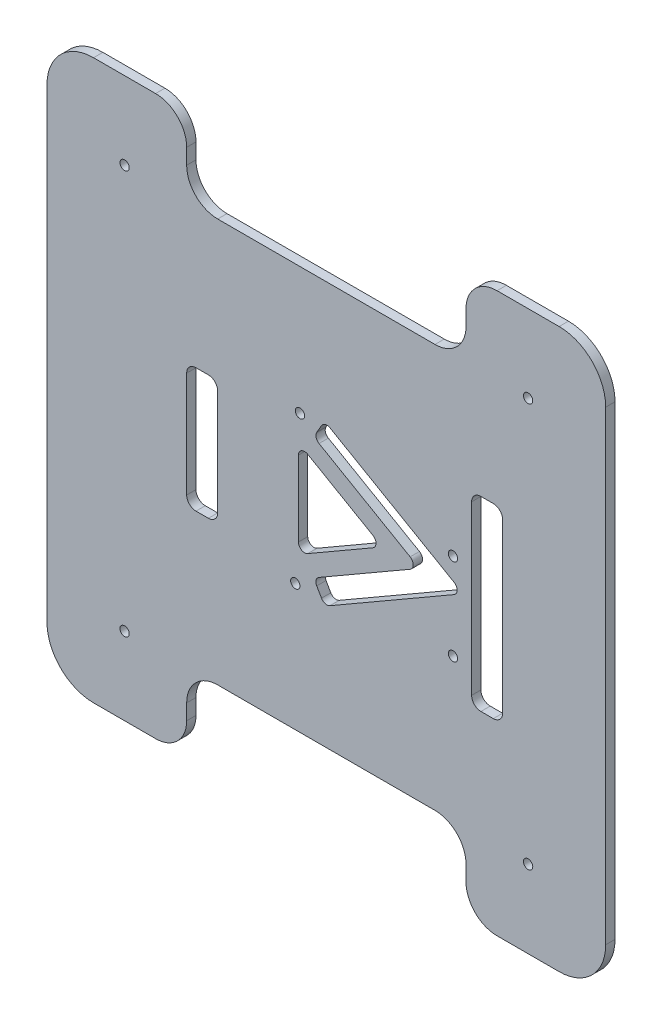
SolidWorks part; units mm, degrees
ref_plane "Front" through (0, 0, 0) normal (0, 0, 1) x (1, 0, 0)
ref_plane "Top" through (0, 0, 0) normal (0, 1, 0) x (1, 0, 0)
ref_plane "Right" through (0, 0, 0) normal (1, 0, 0) x (0, 0, -1)
sketch "Эскиз1" plane through (0, 0, 0) normal (0, 0, 1) x (1, 0, 0)
  line L1 (75, -90) -> (-75, -90)
  line L2 (90, -75) -> (90, 75)
  line L3 (75, 90) -> (-75, 90)
  line L4 (-90, -75) -> (-90, 75)
  line L5 (90, -90) -> (-90, 90) construction
  line L6 (90, 90) -> (-90, -90) construction
  arc A0 (-75, -90) -> (-90, -75) centre (-75, -75) cw
  arc A1 (75, -90) -> (90, -75) centre (75, -75) ccw
  arc A2 (90, 75) -> (75, 90) centre (75, 75) ccw
  arc A3 (-90, 75) -> (-75, 90) centre (-75, 75) cw
  point P0 (0, 0)
  dimension "D3" = 15
  dimension "D1" = 180
  dimension "D2" = 180
extrude "Бобышка-Вытянуть1" add sketch "Эскиз1" along normal blind 3
hole_wizard "Диаметр отверстия Ø3.0 (3)1" positions "Эскиз5" profile "Эскиз4" hole size "Ø3.0" standard "Ansi Metric" end condition up to next
sketch "Эскиз5" plane through (0, 0, 3) normal (0, 0, 1) x (1, 0, 0)
  line L4 (-90, 0) -> (-10, 0) construction
  line L5 (-90, 75) -> (-90, -75) construction
  line L6 (-10, 0) -> (40.8, 0) construction
  line L7 (40.8, 0) -> (90, 0) construction
  line L8 (90, -75) -> (90, 75) construction
  line L10 (-10, -26.65) -> (-10, 26.65) construction
  line L12 (40.8, -19.05) -> (40.8, 8.85) construction
  line L13 (-10, 24.05) -> (-8.5, 24.05) construction
  point P33 (-10, -24.15)
  point P45 (40.8, 8.85)
  point P48 (40.8, -19.05)
  point P59 (-8.5, 24.05)
  dimension "D1" = 53.3
  dimension "D2" = 50.8
  dimension "D3" = 27.9
  dimension "D4" = 2.5
  dimension "D5" = 5.1
  dimension "D6" = 1.5
  dimension "D7" = 80
  dimension "D8" = 15.2
sketch "Эскиз4" plane through (-10, -24.15, 3) normal (1, 0, 0) x (0, -1, 0)
  line L0 (0, 0) -> (0, 3)
  line L1 (0, 3) -> (1.5, 3)
  line L2 (1.5, 3) -> (1.5, 0)
  line L5 (1.5, 0) -> (0, 0)
  line L11 (0, -6.35) -> (0, 107.95) construction
  dimension "Диаметр сквозного отверстия" = 3
  dimension "Глубина сквозного отверстия" = 3
sketch "Эскиз7" plane through (0, 0, 3) normal (0, 0, 1) x (1, 0, 0)
  line L0 (0, -90) -> (0, 90) construction
  line L1 (-75, -90) -> (75, -90) construction
  line L2 (75, 90) -> (-75, 90) construction
  line L4 (45, 65) -> (-45, 65)
  line L5 (45, 65) -> (45, 90)
  line L6 (45, 90) -> (-45, 90)
  line L7 (-45, 65) -> (-45, 90)
  line L8 (45, 65) -> (-45, 90) construction
  line L9 (45, 90) -> (-45, 65) construction
  line L10 (45, -65) -> (-45, -65)
  line L11 (45, -65) -> (45, -90)
  line L12 (45, -90) -> (-45, -90)
  line L13 (-45, -65) -> (-45, -90)
  line L14 (45, -65) -> (-45, -90) construction
  line L15 (45, -90) -> (-45, -65) construction
  point P6 (0, 77.5)
  point P11 (0, -77.5)
  dimension "D1" = 90
  dimension "D2" = 25
extrude "Вырез-Вытянуть1" cut sketch "Эскиз7" against normal through all
fillet "Скругление7" radius 10 8 edges at (45, -90, 1.5) (45, -65, 1.5) (-45, -65, 1.5) (-45, -90, 1.5) (45, 65, 1.5) (45, 90, 1.5) (-45, 90, 1.5) (-45, 65, 1.5)
hole_wizard "Диаметр отверстия Ø3.0 (3)2" positions "Эскиз9" profile "Эскиз8" hole size "Ø3.0" standard "Ansi Metric" end condition up to next
sketch "Эскиз9" plane through (0, 0, 3) normal (0, 0, 1) x (1, 0, 0)
  line L8 (65, -90) -> (65, -65) construction
  line L9 (55, -90) -> (75, -90) construction
  line L10 (65, -65) -> (65, 65) construction
  line L11 (65, 65) -> (65, 90) construction
  line L12 (75, 90) -> (55, 90) construction
  line L14 (-65, 90) -> (-65, 65) construction
  line L15 (-55, 90) -> (-75, 90) construction
  line L16 (-65, 65) -> (-65, -65) construction
  line L17 (-65, -65) -> (-65, -90) construction
  line L18 (-75, -90) -> (-55, -90) construction
  line L20 (-65, -65) -> (-90, -65) construction
  line L21 (-90, 75) -> (-90, -75) construction
  point P50 (-65, -65)
  point P53 (65, -65)
  point P56 (65, 65)
  point P61 (-65, 65)
sketch "Эскиз8" plane through (-65, -65, 3) normal (1, 0, 0) x (0, -1, 0)
  line L0 (0, 0) -> (0, 3)
  line L1 (0, 3) -> (1.5, 3)
  line L2 (1.5, 3) -> (1.5, 0)
  line L5 (1.5, 0) -> (0, 0)
  line L11 (0, -6.35) -> (0, 107.95) construction
  dimension "Диаметр сквозного отверстия" = 3
  dimension "Глубина сквозного отверстия" = 3
sketch "Sketch1" plane through (0, 0, 3) normal (0, 0, 1) x (1, 0, 0)
  line L0 (-40, 0) -> (0, 0) construction
  line L1 (-45, -20) -> (-35, -20)
  line L2 (-45, -20) -> (-45, 20)
  line L3 (-45, 20) -> (-35, 20)
  line L4 (-35, -20) -> (-35, 20)
  line L5 (-45, -20) -> (-35, 20) construction
  line L6 (-45, 20) -> (-35, -20) construction
  line L7 (0, 0) -> (51.8, 0) construction
  line L9 (46.8, -30) -> (56.8, -30)
  line L10 (46.8, -30) -> (46.8, 30)
  line L11 (46.8, 30) -> (56.8, 30)
  line L12 (56.8, -30) -> (56.8, 30)
  line L13 (46.8, -30) -> (56.8, 30) construction
  line L14 (46.8, 30) -> (56.8, -30) construction
  circle A0 centre (40.8, -19.05) radius 1.5 construction
  point P0 (-40, 0)
  dimension "D1" = 10
  dimension "D2" = 40
  dimension "D3" = 40
  dimension "D4" = 6
  dimension "D5" = 60
extrude "Cut-Extrude1" cut sketch "Sketch1" against normal through all
sketch "Sketch3" plane through (0, 0, 3) normal (0, 0, 1) x (1, 0, 0)
  line L0 (15, 1.7321) -> (-6, 13.8564) construction
  line L1 (18, 0) -> (-9, 15.5885)
  line L2 (-9, 15.5885) -> (-9, -15.5885)
  line L3 (-9, -15.5885) -> (18, 0)
  line L4 (30, 0) -> (-4.0928, 19.6835)
  line L6 (-4.0928, 19.6835) -> (-0.5606, 25.8014)
  line L7 (44.1286, 0) -> (-0.5606, 25.8014)
  line L12 (9, 0) -> (44.9942, 0) construction
  line L13 (-4.0928, -19.6835) -> (-0.5606, -25.8014)
  line L14 (44.1286, 0) -> (-0.5606, -25.8014)
  line L15 (30, 0) -> (-4.0928, -19.6835)
  circle A0 centre (0, 0) radius 9 construction
  circle A1 centre (-8.5, 24.05) radius 1.5 construction
  circle A2 centre (40.8, 8.85) radius 1.5 construction
  dimension "D1" = 6
  dimension "D2" = 6
  dimension "D3" = 6
extrude "Cut-Extrude2" cut sketch "Sketch3" against normal through all
fillet "Fillet1" radius 3 8 edges at (-35, 20, 1.5) (-45, 20, 1.5) (-45, -20, 1.5) (-35, -20, 1.5) (56.8, -30, 1.5) (56.8, 30, 1.5) (46.8, 30, 1.5) (46.8, -30, 1.5)
fillet "Fillet2" radius 2 9 edges at (44.1286, 0, 1.5) (30, 0, 1.5) (18, 0, 1.5) (-0.5606, 25.8014, 1.5) (-4.0928, 19.6835, 1.5) (-9, 15.5885, 1.5) (-4.0928, -19.6835, 1.5) (-0.5606, -25.8014, 1.5) (-9, -15.5885, 1.5)
